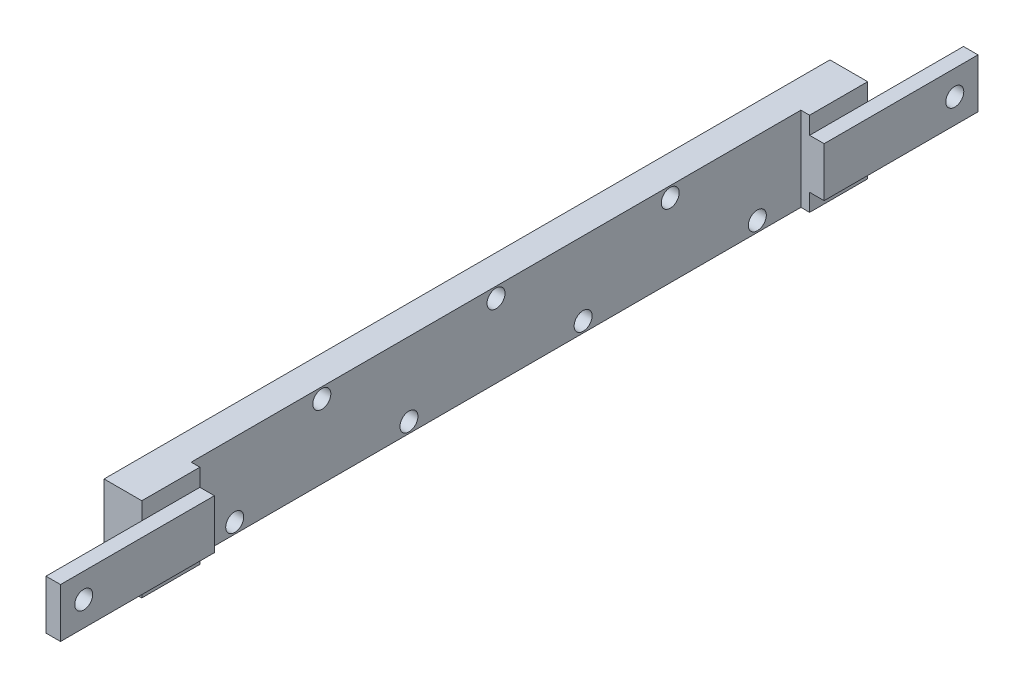
SolidWorks part; units mm, degrees
ref_plane "前视基准面" through (0, 0, 0) normal (0, 0, 1) x (1, 0, 0)
ref_plane "上视基准面" through (0, 0, 0) normal (0, 1, 0) x (1, 0, 0)
ref_plane "右视基准面" through (0, 0, 0) normal (1, 0, 0) x (0, 0, -1)
other "Configuration Table"
sketch "草图1" plane through (0, 0, 0) normal (1, 0, 0) x (0, 0, -1)
  line L0 (-150, 0) -> (150, 0) construction
  line L1 (-125, 14.5) -> (125, 14.5)
  line L2 (-125, 14.5) -> (-125, -14.5)
  line L3 (-125, -14.5) -> (125, -14.5)
  line L4 (125, 14.5) -> (125, -14.5)
  line L8 (-120, 10.8586) -> (120, 10.8586)
  line L9 (-120, 10.8586) -> (-120, -10.8586)
  line L10 (-120, -10.8586) -> (120, -10.8586)
  line L11 (120, 10.8586) -> (120, -10.8586)
  line L12 (-120, 10.8586) -> (120, -10.8586) construction
  line L13 (-120, -10.8586) -> (120, 10.8586) construction
  circle A2 centre (-90, -10.8586) radius 3.1
  circle A3 centre (-30, -10.8586) radius 3.1
  circle A4 centre (30, -10.8586) radius 3.1
  circle A5 centre (-60, 10.8586) radius 3.1
  circle A6 centre (90, -10.8586) radius 3.1
  circle A7 centre (0, 10.8586) radius 3.1
  circle A8 centre (60, 10.8586) radius 3.1
  point P10 (0, 0)
  point P12 (-125, 0)
  point P29 (-100.2427, -10.8586)
  point P30 (-71.2579, -10.8586)
  point P31 (15.2133, -10.8586)
  point P32 (69.9622, -10.8586)
  point P33 (-83.979, 10.8586)
  point P34 (22.1374, 10.8586)
  point P35 (84.9943, 10.8586)
  dimension "D2" = 5
  dimension "D8" = 6.2
  dimension "D1" = 300
  dimension "D3" = 5
  dimension "D5" = 14.5
  dimension "D6" = 120
  dimension "D7" = 10.8586
  dimension "D9" = 30
  dimension "D10" = 60
  dimension "D11" = 60
  dimension "D12" = 60
  dimension "D13" = 60
  dimension "D14" = 60
  dimension "D15" = 60
  dimension "D16" = 60
  dimension "D17" = 30
extrude "凸台-拉伸1" add sketch "草图1" along normal blind 10 contours L1 L4 L3 L2
extrude "切除-拉伸1" cut sketch "草图1<3>" along normal through all contours A2 | A3 | A4 | A6 | A8 | A7 | A5
sketch "草图1<3>" plane through (0, 0, 0) normal (1, 0, 0) x (0, 0, -1) same geometry as "草图1"
sketch "草图3" plane through (10, 0, 0) normal (1, 0, 0) x (0, 0, -1)
  line L0 (-125, 14.5) -> (125, 14.5) construction
  line L1 (105, 14.5) -> (125, 14.5)
  line L2 (105, 14.5) -> (105, -14.5)
  line L3 (105, -14.5) -> (125, -14.5)
  line L4 (125, 14.5) -> (125, -14.5)
  line L5 (125, 14.5) -> (125, -14.5) construction
  line L6 (-125, -14.5) -> (125, -14.5) construction
  line L7 (-125, 14.5) -> (-105, 14.5)
  line L8 (-125, 14.5) -> (-125, -14.5)
  line L9 (-125, -14.5) -> (-105, -14.5)
  line L10 (-105, 14.5) -> (-105, -14.5)
  dimension "D1" = 20
  dimension "D2" = 20
extrude "凸台-拉伸2" add sketch "草图3" along normal blind 3 contours L10 L9 L8 L7 | L2 L3 L4 L1
sketch "草图4" plane through (13, 0, 0) normal (1, 0, 0) x (0, 0, -1)
  line L0 (105, 14.5) -> (105, -14.5) construction
  line L1 (105, 8.5) -> (158, 8.5)
  line L2 (105, 8.5) -> (105, -8.5)
  line L3 (105, -8.5) -> (158, -8.5)
  line L4 (158, 8.5) -> (158, -8.5)
  line L5 (105, 14.5) -> (125, 14.5) construction
  line L6 (105, -14.5) -> (125, -14.5) construction
  line L7 (-105, 14.5) -> (-105, -14.5) construction
  line L8 (-105, 8.5) -> (-158, 8.5)
  line L9 (-105, 8.5) -> (-105, -8.5)
  line L10 (-105, -8.5) -> (-158, -8.5)
  line L11 (-158, 8.5) -> (-158, -8.5)
  circle A1 centre (150, 0) radius 3.1
  circle A2 centre (-150, 0) radius 3.1
  point P22 (0, 0)
  dimension "D2" = 6.2
  dimension "D1" = 53
  dimension "D3" = 6
  dimension "D4" = 6
  dimension "D5" = 300
extrude "凸台-拉伸3" add sketch "草图4" along normal blind 5 contours L10 L11 L8 L9 | L3 L4 L1 L2 | A2 | A1
